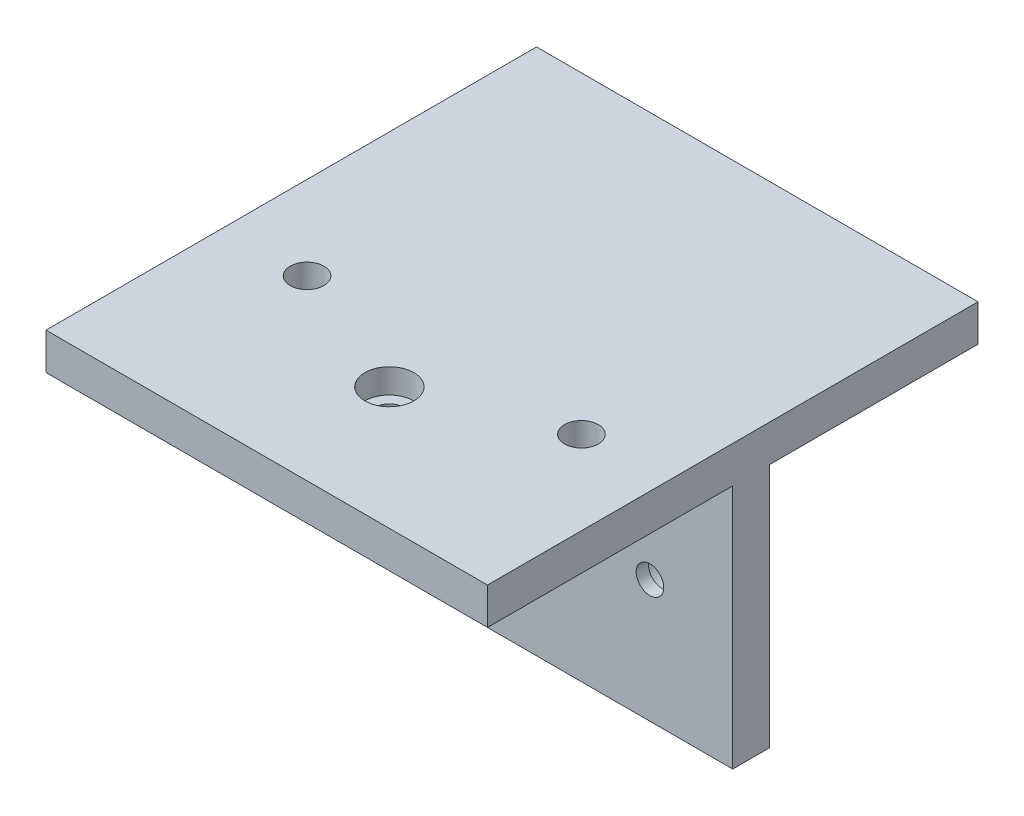
SolidWorks part; units mm, degrees
ref_plane "Front Plane" through (0, 0, 0) normal (0, 0, 1) x (1, 0, 0)
ref_plane "Top Plane" through (0, 0, 0) normal (0, 1, 0) x (1, 0, 0)
ref_plane "Right Plane" through (0, 0, 0) normal (1, 0, 0) x (0, 0, -1)
sketch "Sketch1" plane through (0, 0, 0) normal (1, 0, 0) x (0, 0, -1)
  line L0 (-20, 20) -> (20, 20)
  line L1 (-20, 20) -> (20, 20) construction
  line L2 (-20, 20) -> (-20, -20) construction
  line L3 (-20, -20) -> (20, -20) construction
  line L4 (20, 20) -> (20, -20) construction
  line L5 (-20, 20) -> (20, -20) construction
  line L6 (-20, -20) -> (20, 20) construction
  line L7 (20, 20) -> (20, -20)
  line L8 (26, 20) -> (60, 20)
  line L10 (-20, 20) -> (-20, 26)
  line L11 (-20, 26) -> (60, 26)
  line L12 (60, 26) -> (60, 20)
  line L13 (20, -20) -> (26, -20)
  line L14 (26, -20) -> (26, 20)
  point P0 (0, 0)
  point P6 (0, 0)
  dimension "D1" = 40
  dimension "D2" = 40
  dimension "D3" = 6
  dimension "D4" = 6
extrude "Boss-Extrude1" add sketch "Sketch1" along normal mid plane 72 contours L12 L11 L10 L0 L8 region at (0, 15.3333, -21)
sketch "Sketch2" plane through (0, 0, -26) normal (0, 0, -1) x (-1, 0, 0)
  line L0 (-22.5, 20) -> (-22.5, -20) construction
  line L1 (-36, 20) -> (36, 20) construction
  line L2 (-36, -20) -> (36, -20) construction
  line L3 (22.5, 20) -> (22.5, -20) construction
  line L4 (-36, 20) -> (36, 20) construction
  line L6 (22.5, -20) -> (-22.5, -20) construction
  circle A0 centre (-22.5, 0) radius 2.25
  circle A1 centre (22.5, 0) radius 2.25
  point P10 (0, -20)
  dimension "D2" = 4.5
  dimension "D1" = 45
extrude "Cut-Extrude1" cut sketch "Sketch2" against normal up to next
sketch "Sketch3" plane through (0, 20, 0) normal (0, -1, 0) x (1, 0, 0)
  circle A0 centre (0, 0) radius 2.25
  point P0 (0, 0)
  dimension "D2" = 4.5
extrude "Cut-Extrude2" cut sketch "Sketch3" against normal up to next
sketch "Sketch4" plane through (0, 0, -26) normal (0, 0, -1) x (-1, 0, 0)
  circle A0 centre (-22.5, 0) radius 4
  circle A1 centre (22.5, 0) radius 4
  dimension "D1" = 8
extrude "Cut-Extrude3" cut sketch "Sketch4" against normal blind 4
sketch "Sketch5" plane through (0, 26, 0) normal (0, 1, 0) x (1, 0, 0)
  circle A1 centre (0, 0) radius 4
  dimension "D1" = 8
extrude "Cut-Extrude4" cut sketch "Sketch5" against normal blind 4
sketch "Sketch7" plane through (0, 26, 0) normal (0, 1, 0) x (1, 0, 0)
  line L0 (-22.375, 8.95) -> (22.375, 8.95) construction
  circle A0 centre (-22.375, 8.95) radius 2.25
  circle A1 centre (22.375, 8.95) radius 2.25
  point P2 (0, 8.95)
  dimension "D3" = 4.5
  dimension "D1" = 44.75
  dimension "D2" = 8.95
extrude "Cut-Extrude5" cut sketch "Sketch7" against normal up to next
sketch "Sketch8" plane through (0, 26, 0) normal (0, 1, 0) x (1, 0, 0)
  circle A0 centre (-22.375, 8.95) radius 2.75
  circle A1 centre (22.375, 8.95) radius 2.75
  dimension "D1" = 5.5
extrude "Cut-Extrude6" cut sketch "Sketch8" against normal blind 4
equation "\"ClearHole\"=4.5"
equation "\"D2@Sketch2\"=\"ClearHole\""
equation "\"D2@Sketch3\"=\"ClearHole\""
equation "\"SocketClear\"=8"
equation "\"D1@Sketch4\"=\"SocketClear\""
equation "\"SocketDepth\"=4"
equation "\"D1@Cut-Extrude3\"=\"SocketDepth\""
equation "\"D4@Sketch1\"=\"D3@Sketch1\""
equation "\"Thicknes\"=6"
equation "\"D3@Sketch1\"=\"Thicknes\""
equation "\"D1@Sketch5\"=\"SocketClear\""
equation "\"D3@Sketch7\"=\"ClearHole\""
equation "\"MFourInsert\"=5.5"
equation "\"D1@Sketch8\"=\"MFourInsert\""
